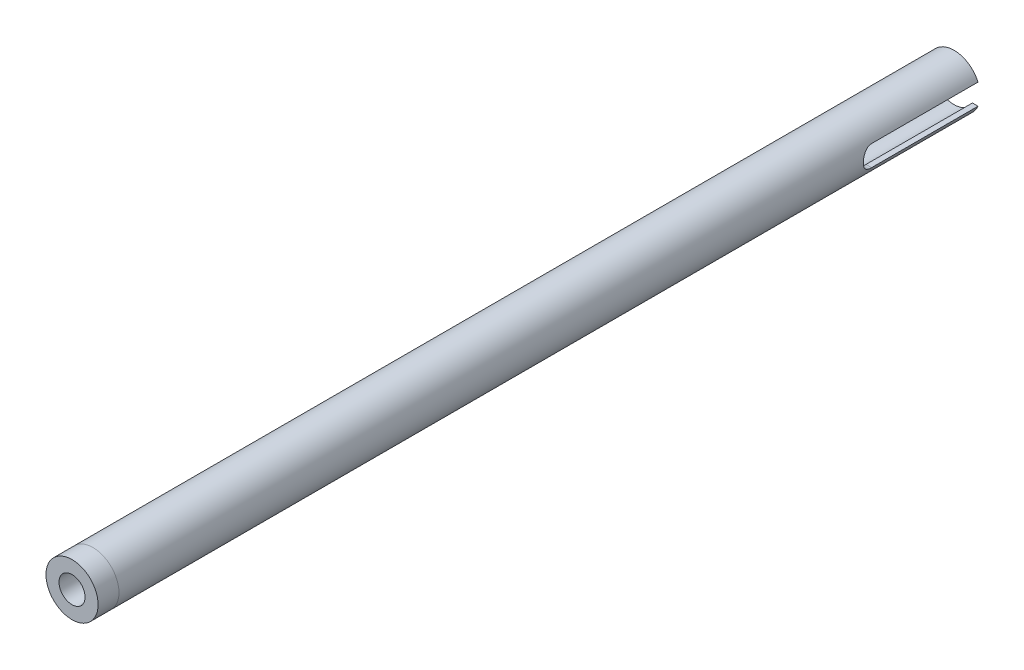
SolidWorks part; units mm, degrees
material "AISI 4130 Steel, annealed at 865C"
ref_plane "Front Plane" through (0, 0, 0) normal (0, 0, 1) x (1, 0, 0)
ref_plane "Top Plane" through (0, 0, 0) normal (0, 1, 0) x (1, 0, 0)
ref_plane "Right Plane" through (0, 0, 0) normal (1, 0, 0) x (0, 0, -1)
sketch "Axis" plane through (0, 0, 0) normal (0, 1, 0) x (1, 0, 0)
  line L0 (0, 0) -> (0, 268.4985) construction
  line L1 (0, 0) -> (0, -34.925) construction
  line L2 (0, 268.4985) -> (-7.9375, 268.4985) construction
  line L3 (0, 290.8401) -> (-10.3188, 261.796) construction
  dimension "D1" = 34.925
  dimension "D2" = 7.9375
sketch "Sketch1" plane through (0, 0, 0) normal (0, 0, 1) x (1, 0, 0)
  line L0 (-7.9375, 0) -> (7.9375, 0) construction
  line L1 (-7.2748, 3.175) -> (7.2748, 3.175)
  line L2 (-7.2748, -3.175) -> (7.2748, -3.175)
  circle A0 centre (0, 0) radius 7.9375
  circle A1 centre (0, 0) radius 6.4135
  circle A2 centre (0, 0) radius 3.9688
  dimension "D1" = 15.875
  dimension "D3" = 7.9375
  dimension "D2" = 1.524
  dimension "D4" = 6.35
extrude "Threaded insert 1-1" add sketch "Sketch1" against normal blind 6.35 contours A2 L1 A1 | A1 L1 A0 | A2 L0 A1 L1 | A1 L0 A0 L1 | L0 A1 L2 A0 | L0 A2 L2 A1 | A2 L2 A1 | A1 L2 A0 | L0 A1 L2 A2 | L0 A0 L2 A1 | A0 L0 A1 L1 | A1 L0 A2 L1 region at (4.7887, 1.6543, 0) region at (4.7887, -1.6543, 0) region at (6.9234, 1.6163, 0) region at (6.9234, -1.6163, 0) region at (-4.7887, -1.6543, 0) region at (-4.7887, 1.6543, 0) region at (0, 4.6159, 0) region at (0, -4.6159, 0) region at (0, 6.5666, 0) region at (6.4237, -3.3281, 0) region at (-6.9234, -1.6163, 0) region at (-6.9234, 1.6163, 0)
extrude "Threaded insert 1-2" add sketch "Sketch1<3>" against normal blind 9.525 from surface contours A2 L1 A1 | A2 L0 A1 L1 | L0 A2 L2 A1 | A2 L2 A1 | L0 A1 L2 A2 | A1 L0 A2 L1 region at (4.7887, 1.6543, 0) region at (4.7887, -1.6543, 0) region at (-4.7887, -1.6543, 0) region at (-4.7887, 1.6543, 0) region at (0, 4.6159, 0) region at (0, -4.6159, 0) starting at face at (7.9375, 0, -6.35)
sketch "Sketch1<3>" plane through (0, 0, 0) normal (0, 0, 1) x (1, 0, 0) same geometry as "Sketch1"
extrude "A-arm tube" add sketch "Sketch1<4>" against normal up to vertex (268.4985 mm away) from surface separate body contours A1 L1 A0 | A1 L0 A0 L1 | L0 A1 L2 A0 | A1 L2 A0 | L0 A0 L2 A1 | A0 L0 A1 L1 region at (6.9234, 1.6163, 0) region at (6.9234, -1.6163, 0) region at (0, 6.5666, 0) region at (6.4237, -3.3281, 0) region at (-6.9234, -1.6163, 0) region at (-6.9234, 1.6163, 0) up to point (0, 0, -268.4985) starting at face at (6.4135, 0, -6.35)
sketch "Sketch1<4>" plane through (0, 0, 0) normal (0, 0, 1) x (1, 0, 0) same geometry as "Sketch1"
extrude "Apex slot" cut sketch "Sketch1<5>" along normal blind 35.56 from surface contours A0 L0 A1 L1 | L0 A0 L2 A1 | A1 L0 A0 L1 | L0 A1 L2 A0 region at (6.9234, 1.6163, 0) region at (6.9234, -1.6163, 0) region at (-6.9234, -1.6163, 0) region at (-6.9234, 1.6163, 0) starting at face at (6.4135, 0, -268.4985)
sketch "Sketch1<5>" plane through (0, 0, 0) normal (0, 0, 1) x (1, 0, 0) same geometry as "Sketch1"
fillet "Fillet1" radius 3.175 4 edges at (-6.4237, 3.175, -232.9385) (-6.4237, -3.175, -232.9385) (6.4237, -3.175, -232.9385) (6.4237, 3.175, -232.9385)
equation "\"tube diameter\"= 5 / 8"
equation "\"tube thickness\"= .06"
equation "\"apex thickness\"= .25"
equation "\"tube slot\"= 1.4"
equation "\"D1@Sketch1\"=\"tube diameter\""
equation "\"D2@Sketch1\"=\"tube thickness\""
equation "\"threaded insert hole\"= .3125"
equation "\"D3@Sketch1\"=\"threaded insert hole\""
equation "\"D4@Sketch1\"=\"apex thickness\""
equation "\"D1@Apex slot\" = \"tube slot\""
equation "\"D1@Fillet1\"=\"apex thickness\"/2"
